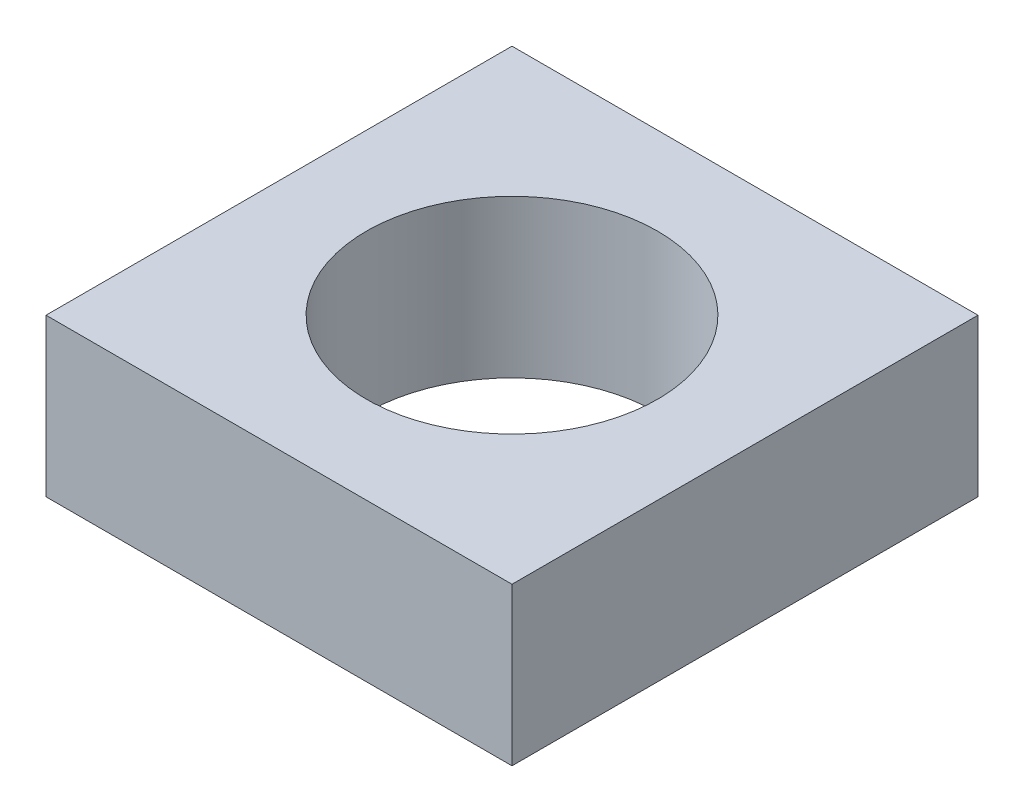
SolidWorks part; units mm, degrees
ref_plane "Front Plane" through (0, 0, 0) normal (0, 0, 1) x (1, 0, 0)
ref_plane "Top Plane" through (0, 0, 0) normal (0, 1, 0) x (1, 0, 0)
ref_plane "Right Plane" through (0, 0, 0) normal (1, 0, 0) x (0, 0, -1)
sketch "Sketch1" plane through (0, 0, 0) normal (0, 1, 0) x (1, 0, 0)
  line L1 (-4, 2.3094) -> (-4, -4.1064) construction
  line L4 (4, -2.3094) -> (4, 4.1064) construction
  line L7 (-4, 4) -> (4, 4)
  line L8 (-4, 4) -> (-4, -4)
  line L9 (-4, -4) -> (4, -4)
  line L10 (4, 4) -> (4, -4)
  line L11 (26.503, -10.6827) -> (20.9468, -7.4748) [skipped]
  line L12 (22.503, 17.6109) -> (16.9468, 14.403) [skipped]
  line L13 (0, -4.6188) -> (5.5562, -1.4109) [skipped]
  line L14 (-4, -2.3094) -> (1.5562, -5.5173) [skipped]
  circle A0 centre (0, 0) radius 4 construction
  circle A1 centre (0, 0) radius 2.5
  dimension "Thread Size" = 5
  dimension "Hex" = 8
extrude "Boss-Extrude1" add sketch "Sketch1" along normal mid plane 2.7
sketch "Sketch2" plane through (0, 1.35, 0) normal (0, 1, 0) x (1, 0, 0)
  circle A1 centre (0, 0) radius 2.5
  circle A3 centre (0, 0) radius 2.5 construction
curve "Helix/Spiral1" [suppressed] pitch 0.8 height 3.5 turns 4.375 parameters "Pitch"=0.8
sketch "Sketch3" [suppressed] plane through (0, 0, 0) normal (1, 0, 0) x (0, 0, -1)
  line L0 (1.9804, 1.75) -> (2.5, 2.05)
  line L1 (2.5, 2.05) -> (2.5, 1.35)
  line L2 (2.5, 1.35) -> (1.9804, 1.65)
  line L3 (1.9804, 1.65) -> (1.9804, 1.75)
  line L4 (2.2402, 1.9) -> (2.2402, 1.5) construction
  line L5 (1.9804, 1.7) -> (2.5, 1.7) construction
  line L6 (2.5, 1.35) -> (-2.5, 1.35) construction
  dimension "D1" = 60
  dimension "D2" = 0.1
sweep "Sweep1" [suppressed] add profiles "Sketch3" path "Helix/Spiral1"
sketch "Sketch4" [suppressed] plane through (0, 1.35, 0) normal (0, 1, 0) x (1, 0, 0)
  circle A1 centre (0, 0) radius 2.5
  circle A2 centre (0, 0) radius 2.5
  dimension "D1" = 0
extrude "Cut-Extrude1" [suppressed] cut sketch "Sketch4" along normal through all and the other way through all draft 45
mirror "Mirror1" [suppressed] about plane through (0, 0, 0) normal (0, 1, 0)
ref_axis "Center Axis 1" through (0, -3.1931, 0) along (0, 1, 0)
ref_plane "Contact Plane 1" through (0, -1.35, 0) normal (0, -1, 0) x (-1, 0, 0)
equation "\"D2@Sketch3\" = \"Pitch@Helix/Spiral1\"*.125"
equation "\"D3@Sketch3\" = \"Pitch@Helix/Spiral1\"*.5"
equation "\"D3@Helix/Spiral1\" = \"Height@Boss-Extrude1\"+\"Pitch@Helix/Spiral1\""
